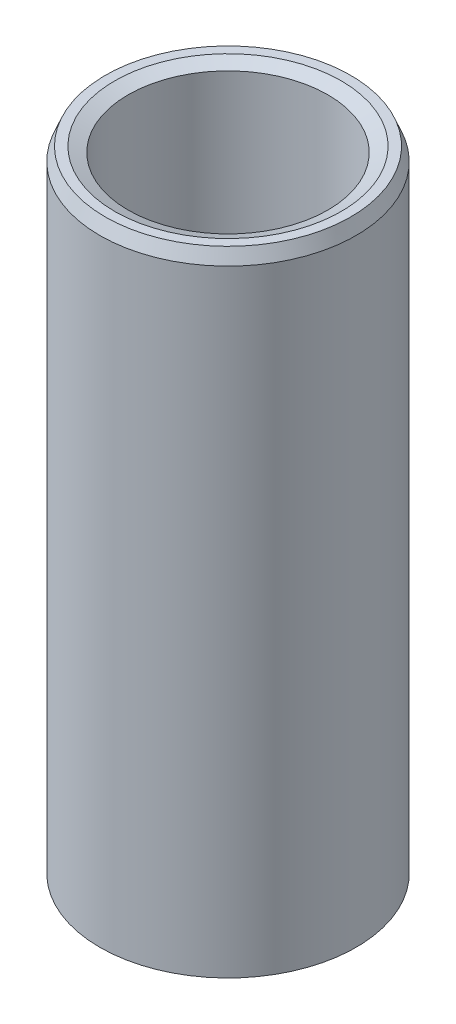
SolidWorks part; units mm, degrees
ref_plane "Front Plane" through (0, 0, 0) normal (0, 0, 1) x (1, 0, 0)
ref_plane "Top Plane" through (0, 0, 0) normal (0, 1, 0) x (1, 0, 0)
ref_plane "Right Plane" through (0, 0, 0) normal (1, 0, 0) x (0, 0, -1)
sketch "Sketch1" plane through (0, 0, 0) normal (0, 1, 0) x (1, 0, 0)
  circle A0 centre (0, 0) radius 35
  dimension "SLEEVE_OD" = 70
extrude "Boss-Extrude1" add sketch "Sketch1" along normal blind 173.4857
sketch "Sketch2" plane through (0, 0, 0) normal (0, 1, 0) x (1, 0, 0)
  circle A0 centre (0, 0) radius 27.2797
  dimension "BORE_D" = 54.5594
extrude "Cut-Extrude1" cut sketch "Sketch2" along normal through all
chamfer "Chamfer1" distance 3.6406 angle 22.194 4 edges at (0, 173.4857, 27.2797) (0, 0, 27.2797) (0, 0, 35) (0, 173.4857, 35) first distance on face at (0, 173.4857, 27.2797) first distance on face at (0, 0, 27.2797) first distance on face at (0, 173.4857, 35)
